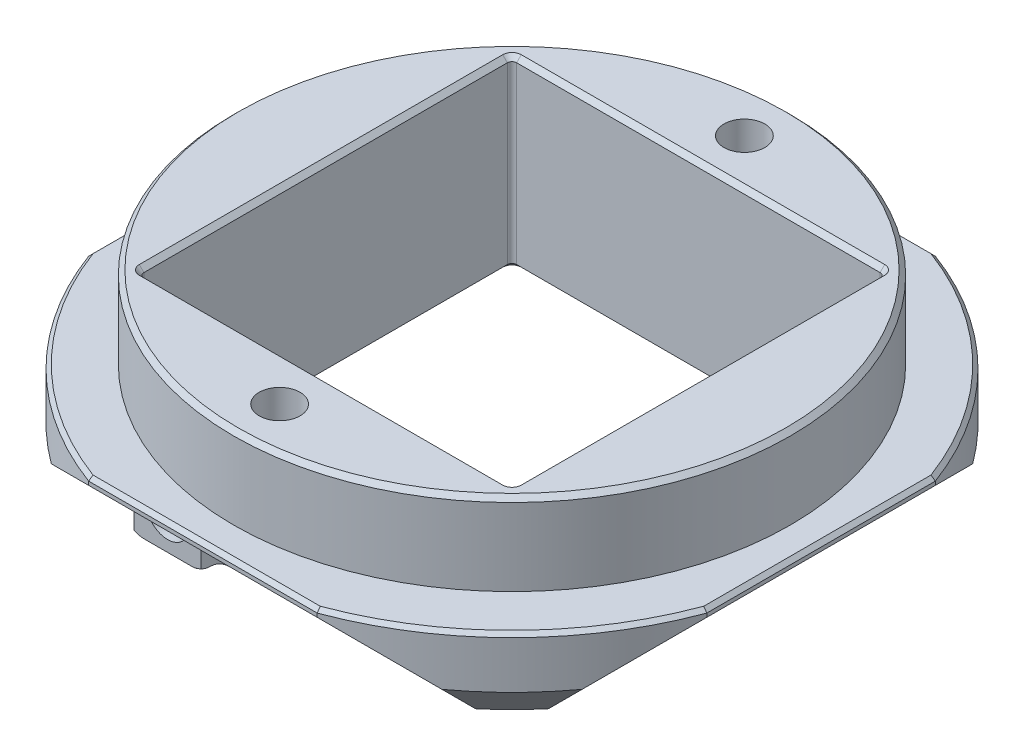
SolidWorks part; units mm, degrees
ref_plane "Front" through (0, 0, 0) normal (0, 0, 1) x (1, 0, 0)
ref_plane "Top" through (0, 0, 0) normal (0, 1, 0) x (1, 0, 0)
ref_plane "Right" through (0, 0, 0) normal (1, 0, 0) x (0, 0, -1)
sketch "Skizze1" plane through (0, 0, 0) normal (0, 1, 0) x (1, 0, 0)
  line L0 (0, 0) -> (0, -7.6976) construction
  line L6 (-20.05, -20.05) -> (20.05, -20.05)
  line L16 (-20.05, -20.05) -> (-20.05, 20.05)
  line L43 (-20.05, 20.05) -> (20.05, 20.05)
  line L45 (20.05, -20.05) -> (20.05, 20.05)
  line L46 (-20.05, -20.05) -> (20.05, 20.05) construction
  line L48 (-20.05, 20.05) -> (20.05, -20.05) construction
  circle A0 centre (0, 0) radius 29.95
  point P0 (0, 0)
  dimension "D2" = 59.9
  dimension "D1" = 40.1
extrude "Aufsatz-Linear austragen1" add sketch "Skizze1" along normal blind 40 contours A0 L16 region at (-29.1029, 0, 0)
ref_plane "Ebene1" through (23.05, 0, 0) normal (-1, 0, 0) x (0, 0, 1)
sketch "Skizze3" plane through (23.05, 0, 0) normal (-1, 0, 0) x (0, 0, 1)
  line L0 (0, 0) -> (0, 40) construction
  line L2 (29.95, 40) -> (-29.95, 40) construction
  circle A0 centre (0, 35) radius 2.875
  dimension "D1" = 5.75
  dimension "D2" = 5
extrude "Schnitt-Linear austragen1" cut sketch "Skizze3" along normal up to next and the other way blind 10
sketch "Skizze4" plane through (23.05, 0, 0) normal (-1, 0, 0) x (0, 0, 1)
  line L0 (-29.95, 20) -> (29.95, 20) construction
  line L1 (-29.95, 40) -> (-29.95, 0) construction
  line L2 (29.95, 0) -> (29.95, 40) construction
  line L3 (-29.95, 29) -> (29.95, 29)
  line L4 (29.95, 29) -> (29.95, 40)
  line L5 (29.95, 40) -> (-29.95, 40)
  line L6 (-29.95, 40) -> (-29.95, 29)
  line L7 (-29.95, 0) -> (-29.95, 11)
  line L8 (29.95, 0) -> (-29.95, 0)
  line L9 (29.95, 11) -> (29.95, 0)
  line L10 (-29.95, 11) -> (29.95, 11)
  dimension "D2" = 18
extrude "Schnitt-Linear austragen2" cut sketch "Skizze4" against normal blind 10
pattern_circular "Kreismuster1" count 2 over 360 about axis through (0, 40, 0) along (0, -1, 0) of "Schnitt-Linear austragen1" reverse direction yes
pattern_circular "Kreismuster2" count 4 over 360 about axis through (0, 40, 0) along (0, -1, 0) of "Schnitt-Linear austragen2" reverse direction yes
sketch "Skizze5" plane through (0, 0, 23.05) normal (0, 0, 1) x (1, 0, 0)
  line L0 (0, 0) -> (0, 11) construction
  line L1 (-19.1233, 11) -> (19.1233, 11) construction
  line L2 (0, 0) -> (-20, 0) construction
  line L3 (-19.1233, 0) -> (19.1233, 0) construction
  line L4 (-10, 0) -> (-10, 11) construction
  circle A2 centre (-10, 5.5) radius 2.3
  circle A3 centre (10, 5.5) radius 2.3
  dimension "D1" = 10
  dimension "D2" = 4.6
extrude "Schnitt-Linear austragen3" cut sketch "Skizze5" against normal through all from surface contours A3 region at (10, 5.5, 23.05) starting at face at (0, 20, -20.05)
extrude "Schnitt-Linear austragen11" cut sketch "Skizze5<3>" against normal blind 10 contours A2 region at (-10, 5.5, 23.05)
sketch "Skizze5<3>" plane through (0, 0, 23.05) normal (0, 0, 1) x (1, 0, 0) same geometry as "Skizze5"
sketch "Skizze9" plane through (0, 11, 0) normal (0, -1, 0) x (1, 0, 0)
  line L0 (-20.05, 20.05) -> (-20.05, -20.05) construction
  line L1 (-20.05, 20.05) -> (20.05, 20.05)
  line L2 (-20.05, 20.05) -> (-20.05, -20.05)
  line L3 (-20.05, -20.05) -> (20.05, -20.05)
  line L4 (20.05, 20.05) -> (20.05, -20.05)
  circle A0 centre (0, 0) radius 35.45
  arc A1 (23.05, -19.1233) -> (23.05, 19.1233) centre (0, 0) ccw construction
  dimension "D1" = 5.5
extrude "Aufsatz-Linear austragen2" add sketch "Skizze9" along normal blind 0.8
chamfer "Fase1" distance 10.2 angle 45 8 edges at (0, 10.2, -23.05) (21.1778, 10.2, -21.1778) (23.05, 10.2, 0) (21.1778, 10.2, 21.1778) (0, 10.2, 23.05) (-21.1778, 10.2, -21.1778) (-21.1778, 10.2, 21.1778) (-23.05, 10.2, 0)
ref_plane "Ebene2" through (0, 0, -27.05) normal (0, 0, 1) x (1, 0, 0)
sketch "Skizze10" plane through (0, 0, -27.05) normal (0, 0, 1) x (1, 0, 0)
  line L0 (0, 0) -> (0, 12.5763) construction
  circle A0 centre (10, 5.5) radius 3.9
  circle A2 centre (-10, 5.5) radius 3.9
  dimension "D1" = 7.8
extrude "Schnitt-Linear austragen6" cut sketch "Skizze10" against normal through all contours A0 region at (10, 5.5, -27.05)
ref_plane "Ebene3" through (0, 0, 27.05) normal (0, 0, -1) x (-1, 0, 0)
extrude "Schnitt-Linear austragen10" cut sketch "Skizze10<4>" along normal blind 10 from surface contours A2 region at (-10, 5.5, -27.05) starting at plane "Ebene3"
sketch "Skizze10<4>" plane through (0, 0, -27.05) normal (0, 0, 1) x (1, 0, 0) same geometry as "Skizze10"
sketch "Skizze11" plane through (0, 0, 0) normal (0, 0, 1) x (1, 0, 0)
  line L0 (0, 40) -> (0, 0) construction
  line L1 (19.1233, 40) -> (-19.1233, 40) construction
  line L2 (0, 20) -> (-37.3482, 20) construction
  line L4 (-30.2129, 19.8) -> (0, 19.8)
  line L5 (-30.2129, 19.8) -> (-30.2129, 45.953)
  line L6 (-30.2129, 45.953) -> (36.6228, 45.953)
  line L7 (36.6228, 45.953) -> (36.6228, 19)
  line L8 (36.6228, 19) -> (31.1372, 19.8)
  line L9 (31.1372, 19.8) -> (0, 19.8)
  dimension "D1" = 0.4
extrude "Schnitt-Linear austragen7" cut sketch "Skizze11" against normal through all and the other way through all
sketch "Skizze12" plane through (0, 10.2, 0) normal (0, -1, 0) x (1, 0, 0)
  line L0 (12.2939, 33.25) -> (-12.2939, 33.25)
  line L1 (-12.2939, 33.25) -> (-29.7259, 33.25)
  line L2 (-29.7259, 33.25) -> (-33.25, 12.2939)
  line L3 (-33.25, 12.2939) -> (-33.25, -12.2939)
  line L4 (-33.25, -12.2939) -> (-31.7681, -32.1539)
  line L5 (-31.7681, -32.1539) -> (-17.93, -35.5688)
  line L6 (-17.93, -35.5688) -> (-12.2939, -33.25)
  line L7 (-12.2939, -33.25) -> (12.2939, -33.25)
  line L8 (12.2939, -33.25) -> (52.2706, -39.9727)
  line L9 (52.2706, -39.9727) -> (33.25, -12.2939)
  line L10 (33.25, -12.2939) -> (33.25, 12.2939)
  line L11 (33.25, 12.2939) -> (40.5984, 38.9085)
  line L12 (40.5984, 38.9085) -> (12.2939, 33.25)
  circle A0 centre (0, 0) radius 68.3883
extrude "Schnitt-Linear austragen8" cut sketch "Skizze12" against normal through all
sketch "Skizze13" plane through (0, 19.8, 0) normal (0, 1, 0) x (1, 0, 0)
  line L0 (0, 0) -> (0, 15.9968) construction
  line L1 (0, 20.05) -> (0, 25) construction
  line L2 (0, 25) -> (0, 29.95) construction
  line L3 (20.05, 20.05) -> (-20.05, 20.05) construction
  line L4 (0, 0) -> (-8.9639, 0) construction
  circle A0 centre (0, 25) radius 2.2
  circle A1 centre (0, -25) radius 2.2
  circle A2 centre (0, 0) radius 29.95 construction
  dimension "D1" = 4.4
extrude "Schnitt-Linear austragen9" cut sketch "Skizze13" against normal blind 7
fillet "Verrundung2" radius 0.5 4 edges at (20.05, 9.9, 20.05) (-20.05, 9.9, 20.05) (-20.05, 9.9, -20.05) (20.05, 9.9, -20.05)
chamfer "Fase4" distance 0.5 angle 45 17 edges at (29.95, 19.8, 0) (0, 19.8, 20.05) (-20.05, 19.8, 0) (0, 19.8, -20.05) (20.05, 19.8, 0) (-19.9036, 19.8, -19.9036) (-19.9036, 19.8, 19.9036) (19.9036, 19.8, -19.9036) (19.9036, 19.8, 19.9036) (20.05, 0, 0) (19.9036, 0, 19.9036) (19.9036, 0, -19.9036) (0, 0, 20.05) (0, 0, -20.05) (-19.9036, 0, 19.9036) (-19.9036, 0, -19.9036) (-20.05, 0, 0)
chamfer "Fase3" distance 0.4 angle 45 8 edges at (25.0669, 11, 25.0669) (0, 11, 33.25) (-25.0669, 11, 25.0669) (-33.25, 11, 0) (-25.0669, 11, -25.0669) (0, 11, -33.25) (25.0669, 11, -25.0669) (33.25, 11, 0)
sketch "Skizze14" plane through (0, 0, -27.05) normal (0, 0, -1) x (-1, 0, 0)
  line L0 (-6.4, 4) -> (-6.4, 0)
  line L1 (-19.1233, 0) -> (19.1233, 0) construction
  line L2 (-13.6, 4) -> (-13.6, 0)
  line L3 (-13.6, 0) -> (-6.4, 0)
  line L4 (-13.6, 4) -> (-11.7436, 4)
  line L5 (-11.7436, 4) -> (-13.6, 4) construction
  line L6 (-8.2564, 4) -> (-6.4, 4)
  line L7 (0, 0) -> (0, 14.0629) construction
  line L8 (13.6, 4) -> (11.7436, 4)
  line L9 (8.2564, 4) -> (6.4, 4)
  line L10 (6.4, 4) -> (6.4, 0)
  line L11 (13.6, 0) -> (6.4, 0)
  line L12 (13.6, 4) -> (13.6, 0)
  arc A0 (-11.7436, 4) -> (-8.2564, 4) centre (-10, 5.5) ccw
  arc A2 (-8.2564, 4) -> (-11.7436, 4) centre (-10, 5.5) ccw construction
  arc A4 (11.7436, 4) -> (8.2564, 4) centre (10, 5.5) cw
  line M10 (-13.6, 4) -> (-11.7436, 4)
  line M12 (-8.2564, 4) -> (-6.4, 4)
extrude "Aufsatz-Linear austragen5" add sketch "Skizze14" against normal up to surface contours A0 L2 L3 L0 M10 M12 region at (10, 1.8793, -27.05) up to face at (0.3152, 5.3354, -28.3854)
extrude "Aufsatz-Linear austragen6" add sketch "Skizze14<4>" along normal up to surface from surface contours L8 A4 L9 L10 L11 L12 region at (-10, 1.8793, -27.05) up to face at (0.3152, 5.3354, 28.3854) starting at face at (-10, 6.3, 27.05)
sketch "Skizze14<4>" plane through (0, 0, -27.05) normal (0, 0, -1) x (-1, 0, 0) same geometry as "Skizze14"
chamfer "Fase5" distance 2 angle 45 6 edges at (-6.4, 0, 25.05) (-10, 0, 27.05) (-13.6, 0, 25.05) (6.4, 0, -25.05) (10, 0, -27.05) (13.6, 0, -25.05)
fillet "Verrundung1" radius 1.41 8 edges at (-7.4, 1, 24.05) (-7.4, 1, 26.05) (-12.6, 1, 26.05) (-12.6, 1, 24.05) (7.4, 1, -24.05) (7.4, 1, -26.05) (12.6, 1, -26.05) (12.6, 1, -24.05)
